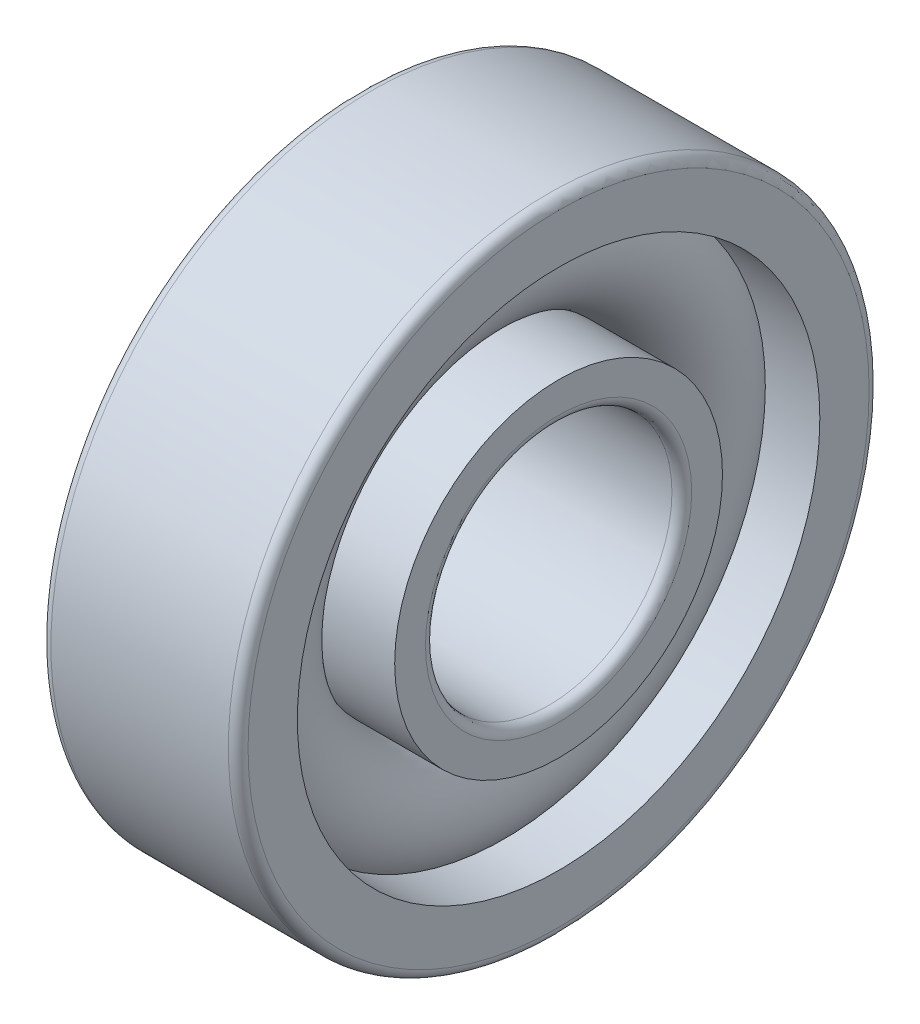
SolidWorks part; units mm, degrees
ref_plane "Plane1" through (0, 0, 0) normal (0, 0, 1) x (1, 0, 0)
ref_plane "Plane2" through (0, 0, 0) normal (0, 1, 0) x (1, 0, 0)
ref_plane "Plane3" through (0, 0, 0) normal (1, 0, 0) x (0, 0, -1)
sketch "Clipboard" plane through (0, 0, 0) normal (0, 0, 1) x (1, 0, 0)
  line L0 (-10, 0) -> (10, 0) construction
  line L1 (0, 0) -> (22.3471, -0.7804)
  line L2 (0, 0) -> (4.4973, 0.157)
  line L3 (0, 0) -> (22.3471, -0.7804)
  line L4 (0, 0) -> (-22.3573, -0.3902)
sketch "CagSpiSke" plane through (0, 0, 0) normal (0, 0, 1) x (1, 0, 0)
  line L0 (0.3, 4.3) -> (0.3, 4.7)
  line L1 (0.3, 4.7) -> (-0.3, 4.7)
  line L2 (-0.3, 4.7) -> (-0.3, 4.3)
  line L3 (-0.3, 4.3) -> (0.3, 4.3)
  line L4 (-20.6375, 0) -> (20.6375, 0) construction
  line L5 (0, 0) -> (0, 23.7692) construction
revolve "CageSpine" add sketch "CagSpiSke" angle 0.001 about L4
ref_axis "Axis1" through (-50, 0, 0) along (1, 0, 0)
sketch "CagBalSke" plane through (0, 0, 0) normal (0, 0, 1) x (1, 0, 0)
  line L0 (-1.32, 4.5) -> (1.32, 4.5)
  line L1 (-1.905, 4.5) -> (1.905, 4.5) construction
  line L2 (-10, 0) -> (10, 0) construction
  line L3 (0, 0) -> (0, 24) construction
  arc A0 (1.32, 4.5) -> (-1.32, 4.5) centre (0, 4.5) cw
revolve "CageBall" [suppressed] add sketch "CagBalSke" angle 360 about L1 reverse direction yes
pattern_circular "CageBalls" [suppressed] count 2 every 180 about axis through (-50, 0, 0) along (1, 0, 0)
sketch "CagTrmODSke" plane through (0, 0, 0) normal (0, 0, 1) x (1, 0, 0)
  line L0 (1.321, 4.7) -> (1.321, 5.821)
  line L1 (1.321, 5.821) -> (-1.321, 5.821)
  line L2 (-1.321, 5.821) -> (-1.321, 4.7)
  line L3 (-1.321, 4.7) -> (1.321, 4.7)
  line L4 (-20.6375, 0) -> (20.6375, 0) construction
  line L5 (0, 0) -> (0, 25) construction
revolve "CageTrimOD" [suppressed] cut sketch "CagTrmODSke" angle 360 about L4 reverse direction yes
sketch "CagTrmIDSke" plane through (0, 0, 0) normal (0, 0, 1) x (1, 0, 0)
  line L0 (1.321, 3.181) -> (1.321, 4.3)
  line L1 (1.321, 4.3) -> (-1.321, 4.3)
  line L2 (-1.321, 4.3) -> (-1.321, 3.181)
  line L3 (-1.321, 3.181) -> (1.321, 3.181)
  line L4 (-20.6375, 0) -> (20.6375, 0) construction
  line L5 (0, 0) -> (0, 25) construction
revolve "CageTrimID" [suppressed] cut sketch "CagTrmIDSke" angle 360 about L4 reverse direction yes
sketch "BalSimSke" plane through (0, 0, 0) normal (0, 0, 1) x (1, 0, 0)
  line L0 (-10, 0) -> (10, 0) construction
  line L1 (-10, 4.5) -> (10, 4.5) construction
  line L2 (0, 0) -> (0, 23) construction
  circle A0 centre (0, 4.5) radius 1.2
revolve "BallsSimplified" add sketch "BalSimSke" angle 360 about L0
sketch "BalDetSke" plane through (0, 0, 0) normal (0, 0, 1) x (1, 0, 0)
  line L0 (-1.2, 4.5) -> (1.2, 4.5)
  line L1 (-1.905, 4.5) -> (1.905, 4.5) construction
  line L2 (0, 0) -> (0, 25) construction
  arc A0 (1.2, 4.5) -> (-1.2, 4.5) centre (0, 4.5) cw
revolve "BallDetailed" [suppressed] add sketch "BalDetSke" angle 360 about L1 reverse direction yes
sketch "InnRacSke" plane through (0, 0, 0) normal (0, 0, 1) x (1, 0, 0)
  line L0 (-0.8606, 3.7) -> (-2, 3.7)
  line L1 (-2, 3.7) -> (-2, 2.7)
  line L2 (-1.8, 2.5) -> (1.8, 2.5)
  line L3 (2, 2.7) -> (2, 3.325)
  line L4 (0, 3.325) -> (2, 3.325)
  line L5 (-20.6375, 0) -> (20.6375, 0) construction
  line L6 (0, 0) -> (0, 30) construction
  arc A0 (-2, 2.7) -> (-1.8, 2.5) centre (-1.8, 2.7) ccw
  arc A1 (1.8, 2.5) -> (2, 2.7) centre (1.8, 2.7) ccw
  arc A2 (0, 3.325) -> (-0.8606, 3.7) centre (0, 4.5) cw
revolve "InnerRace" add sketch "InnRacSke" angle 360 about L5 reverse direction yes
sketch "OutRacSke" plane through (0, 0, 0) normal (0, 0, 1) x (1, 0, 0)
  line L0 (0, 5.675) -> (-2, 5.675)
  line L1 (-2, 5.675) -> (-2, 6.3)
  line L2 (-1.8, 6.5) -> (1.8, 6.5)
  line L3 (2, 6.3) -> (2, 5.3)
  line L4 (2, 5.3) -> (0.8606, 5.3)
  line L5 (-20.6375, 0) -> (20.6375, 0) construction
  line L6 (0, 0) -> (0, 30) construction
  arc A0 (-2, 6.3) -> (-1.8, 6.5) centre (-1.8, 6.3) cw
  arc A1 (1.8, 6.5) -> (2, 6.3) centre (1.8, 6.3) cw
  arc A2 (0.8606, 5.3) -> (0, 5.675) centre (0, 4.5) ccw
revolve "OuterRace" add sketch "OutRacSke" angle 360 about L5 reverse direction yes
pattern_circular "BallsDetailed" [suppressed] count 2 every 180 about axis through (-50, 0, 0) along (1, 0, 0)
equation "\"BallCLRad@Clipboard\" = ( \"OD@OutRacSke\" + \"ID@InnRacSke\" ) / 4"
equation "\"BallCLRad@BalSimSke\" = \"BallCLRad@Clipboard\""
equation "\"BallCLRad@BalDetSke\" = \"BallCLRad@Clipboard\""
equation "\"BallCLRad@InnRacSke\" = \"BallCLRad@Clipboard\""
equation "\"BallCLRad@OutRacSke\" = \"BallCLRad@Clipboard\""
equation "\"Ball_diameter@InnRacSke\" = \"Ball_diameter@BalDetSke\" - 0.05"
equation "\"Ball_diameter@OutRacSke\" = \"Ball_diameter@BalDetSke\" - 0.05"
equation "\"Ball_diameter@BalSimSke\" = \"Ball_diameter@BalDetSke\""
equation "\"Width@OutRacSke\" = \"Width@InnRacSke\""
equation "\"Fillet_radius@OutRacSke\" = \"Fillet_radius@InnRacSke\""
equation "\"Max_count@Clipboard\" = int( 3.14159265 / atn(( \"Ball_diameter@BalDetSke\" / 2) / sqr( \"BallCLRad@Clipboard\"  *  \"BallCLRad@Clipboard\" - ( \"Ball_diameter@BalDetSke\" / 2) *  ( \"Ball_diameter@BalDetSke\" / 2))))"
equation "\"Max_count@Clipboard\" = ((sgn( \"Max_count@Clipboard\" - \"Count@Clipboard\" )-1)*( \"Max_count@Clipboard\" - \"Count@Clipboard\" ))/-2+ \"Count@Clipboard\""
equation "\"Count@BallsDetailed\" = int( \"Show_count@Clipboard\" ) "
equation "\"Count@BallsDetailed\" = ((sgn( \"Count@BallsDetailed\" - \"Max_count@Clipboard\" )-1)*( \"Count@BallsDetailed\" - \"Max_count@Clipboard\" ))/-2+ \"Max_count@Clipboard\""
equation "\"Count@BallsDetailed\" = ((sgn( \"Count@BallsDetailed\" - \"Min_count@Clipboard\" )+1)*( \"Count@BallsDetailed\" - \"Min_count@Clipboard\"))/2 +\"Min_count@Clipboard\""
equation "\"Angle@BallsDetailed\" = 360.0 / \"Max_count@Clipboard\""
equation "\"BallCLRad@CagBalSke\" = \"BallCLRad@Clipboard\""
equation "\"Count@CageBalls\" = \"Count@BallsDetailed\""
equation "\"Angle@CageBalls\" = \"Angle@BallsDetailed\""
equation "\"Angle@CageSpine\" =  \"Angle@CageBalls\" * ( \"Count@CageBalls\" -1 + int( \"Count@CageBalls\" / \"Max_count@Clipboard\" ) )  + 0.001 -  int( \"Count@CageBalls\" / \"Max_count@Clipboard\" ) * 0.001"
equation "\"Angle@CageSpine\" =  \"Angle@CageSpine\" * int( \"Min_count@Clipboard\" / 2) + int(1 / \"Min_count@Clipboard\")  * 0.001"
equation "\"CageWallOD@CagBalSke\" =  \"Ball_diameter@BalDetSke\" * 1.1"
equation "\"Thickness@CagSpiSke\" =  \"Ball_diameter@BalDetSke\" * 0.25"
equation "\"OD@CagTrmODSke\" = \"BallCLRad@Clipboard\" * 2 + \"CageWallOD@CagBalSke\" + 0.002"
equation "\"ID@CagTrmODSke\" = \"BallCLRad@Clipboard\" * 2 + \"Ball_diameter@BalDetSke\" / 6"
equation "\"OD@CagTrmIDSke\" = \"BallCLRad@Clipboard\" * 2 - \"Ball_diameter@BalDetSke\" / 6"
equation "\"ID@CagTrmIDSke\" = \"BallCLRad@Clipboard\" * 2 - \"CageWallOD@CagBalSke\" + 0.002"
equation "\"OD@CagSpiSke\" = \"ID@CagTrmODSke\""
equation "\"ID@CagSpiSke\" = \"OD@CagTrmIDSke\""
equation "\"Width@CagTrmODSke\" = \"CageWallOD@CagBalSke\" + 0.002"
equation "\"Width@CagTrmIDSke\" = \"CageWallOD@CagBalSke\" + 0.002"
